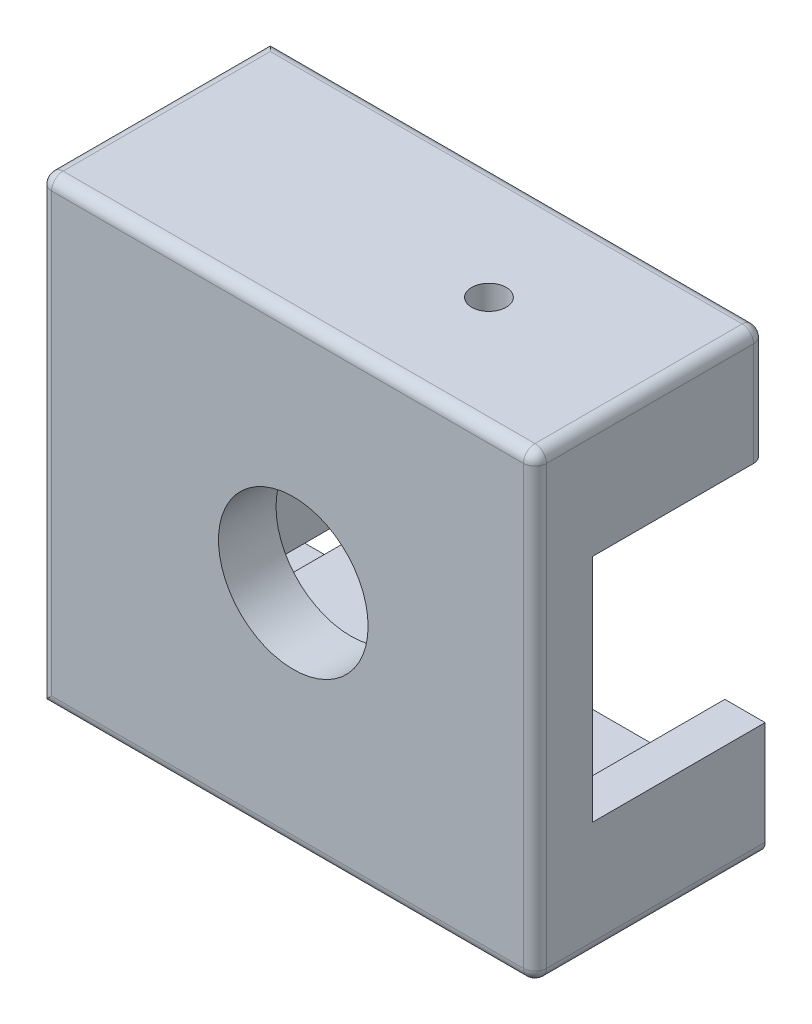
SolidWorks part; units mm, degrees
ref_plane "Front Plane" through (0, 0, 0) normal (0, 0, 1) x (1, 0, 0)
ref_plane "Top Plane" through (0, 0, 0) normal (0, 1, 0) x (1, 0, 0)
ref_plane "Right Plane" through (0, 0, 0) normal (1, 0, 0) x (0, 0, -1)
sketch "Sketch1" plane through (0, 0, 0) normal (0, 0, 1) x (1, 0, 0)
  line L0 (92.0048, 6.2146) -> (46.0048, 6.2146) construction
  line L1 (97.0048, 11.2146) -> (54.0048, 11.2146)
  line L2 (97.0048, 11.2146) -> (97.0048, -28.7854)
  line L3 (97.0048, -28.7854) -> (54.0048, -28.7854)
  line L4 (54.0048, 11.2146) -> (54.0048, -28.7854)
  line L5 (92.0048, 6.2146) -> (92.0048, -1.2854) construction
  dimension "D1" = 40
  dimension "D2" = 43
  dimension "D3" = 5
  dimension "D4" = 5
extrude "Boss-Extrude1" add sketch "Sketch1" along normal blind 5
sketch "Sketch2" plane through (0, 0, 0) normal (0, 0, -1) x (-1, 0, 0)
  line L0 (-97.0048, -28.7854) -> (-97.0048, 11.2146) construction
  line L5 (-72.5048, 0.5146) -> (-85.5048, 0.5146)
  line L6 (-72.5048, 0.5146) -> (-72.5048, -1.4854)
  line L7 (-72.5048, -1.4854) -> (-85.5048, -1.4854)
  line L8 (-85.5048, 0.5146) -> (-85.5048, -1.4854)
  line L13 (-68.0048, -15.9854) -> (-85.5048, -15.9854)
  line L15 (-68.0048, -17.9854) -> (-85.5048, -17.9854)
  line L16 (-85.5048, -15.9854) -> (-85.5048, -17.9854)
  line L17 (-54.0048, -28.7854) -> (-97.0048, -28.7854) construction
  line L18 (-97.0048, 11.2146) -> (-54.0048, 11.2146) construction
  line L19 (-68.0048, -15.9854) -> (-68.0048, -17.9854)
  line L25 (-68.0048, -4.2854) -> (-65.5048, -4.2854)
  line L26 (-68.0048, -4.2854) -> (-68.0048, -14.2854)
  line L27 (-68.0048, -14.2854) -> (-65.5048, -14.2854)
  line L28 (-65.5048, -4.2854) -> (-65.5048, -14.2854)
  point P18 (-66.7548, -14.2854)
  dimension "D1" = 2
  dimension "D2" = 13
  dimension "D3" = 11.5
  dimension "D4" = 10
  dimension "D5" = 2.5
  dimension "D6" = 2
  dimension "D7" = 17.5
  dimension "D8" = 14.5
  dimension "D9" = 10.8
  dimension "D10" = 11.5
  dimension "D11" = 29
  dimension "D12" = 10.7
extrude "Boss-Extrude3" add sketch "Sketch2" along normal blind 8 contours L26 L27 L28 L25 | L19 L15 L16 L13 | L6 L5 L8 L7
sketch "Sketch3" plane through (0, 0, 0) normal (0, 0, -1) x (-1, 0, 0)
  line L0 (-54.0048, 11.2146) -> (-97.0048, 11.2146)
  line L1 (-97.0048, 11.2146) -> (-97.0048, -28.7854)
  line L2 (-97.0048, -28.7854) -> (-54.0048, -28.7854)
  line L3 (-54.0048, -28.7854) -> (-54.0048, -25.2854)
  line L4 (-54.0048, 11.2146) -> (-54.0048, -28.7854) construction
  line L5 (-54.0048, -25.2854) -> (-93.5048, -25.2854)
  line L6 (-93.5048, -25.2854) -> (-93.5048, 7.7146)
  line L7 (-93.5048, 7.7146) -> (-54.0048, 7.7146)
  line L8 (-54.0048, 7.7146) -> (-54.0048, 11.2146)
  dimension "D1" = 3.5
  dimension "D2" = 3.5
  dimension "D3" = 3.5
extrude "Boss-Extrude4" add sketch "Sketch3" along normal blind 15
sketch "Sketch4" plane through (0, 11.2146, 0) normal (0, 1, 0) x (1, 0, 0)
  line L0 (97.0048, -5) -> (97.0048, 15) construction
  line L1 (97.0048, -5) -> (54.0048, -5) construction
  circle A0 centre (83.0048, 5) radius 1.5
  dimension "D1" = 14
  dimension "D2" = 10
  dimension "D3" = 3
extrude "Cut-Extrude1" cut sketch "Sketch4" against normal blind 65
sketch "Sketch6" plane through (0, -28.7854, 0) normal (0, -1, 0) x (1, 0, 0)
  line L0 (54.0048, 5) -> (54.0048, -15) construction
  circle A0 centre (60.0048, -5) radius 1.5
  circle A1 centre (83.0048, -5) radius 1.5 construction
  dimension "D1" = 0
  dimension "D2" = 6
  dimension "D3" = 3
extrude "Cut-Extrude2" cut sketch "Sketch6" against normal blind 10
sketch "Sketch7" plane through (0, 0, 5) normal (0, 0, 1) x (1, 0, 0)
  line L0 (54.0048, 11.2146) -> (54.0048, -28.7854) construction
  line L1 (97.0048, 11.2146) -> (54.0048, 11.2146) construction
  circle A0 centre (76.0048, -8.7854) radius 6.5
  dimension "D1" = 13
  dimension "D2" = 22
  dimension "D3" = 20
extrude "Cut-Extrude3" cut sketch "Sketch7" against normal blind 20
sketch "Sketch8" plane through (97.0048, 0, 0) normal (1, 0, 0) x (0, 0, -1)
  line L0 (15, 11.2146) -> (15, -28.7854) construction
  line L1 (15, 1.2146) -> (0, 1.2146)
  line L2 (15, 1.2146) -> (15, -18.7854)
  line L3 (15, -18.7854) -> (0, -18.7854)
  line L4 (0, 1.2146) -> (0, -18.7854)
  line L5 (-5, -28.7854) -> (-5, 11.2146) construction
  point P8 (-5, -8.7854)
  dimension "D1" = 20
  dimension "D2" = 10
  dimension "D3" = 15
extrude "Cut-Extrude4" cut sketch "Sketch8" against normal blind 5
fillet "Fillet1" radius 1 9 edges at (54.0048, 11.2146, -5) (54.0048, -8.7854, 5) (75.5048, -28.7854, 5) (97.0048, -28.7854, -5) (97.0048, -8.7854, 5) (75.5048, 11.2146, 5) (97.0048, 11.2146, -5) (97.0048, 6.2146, -15) (75.5048, 11.2146, -15)
